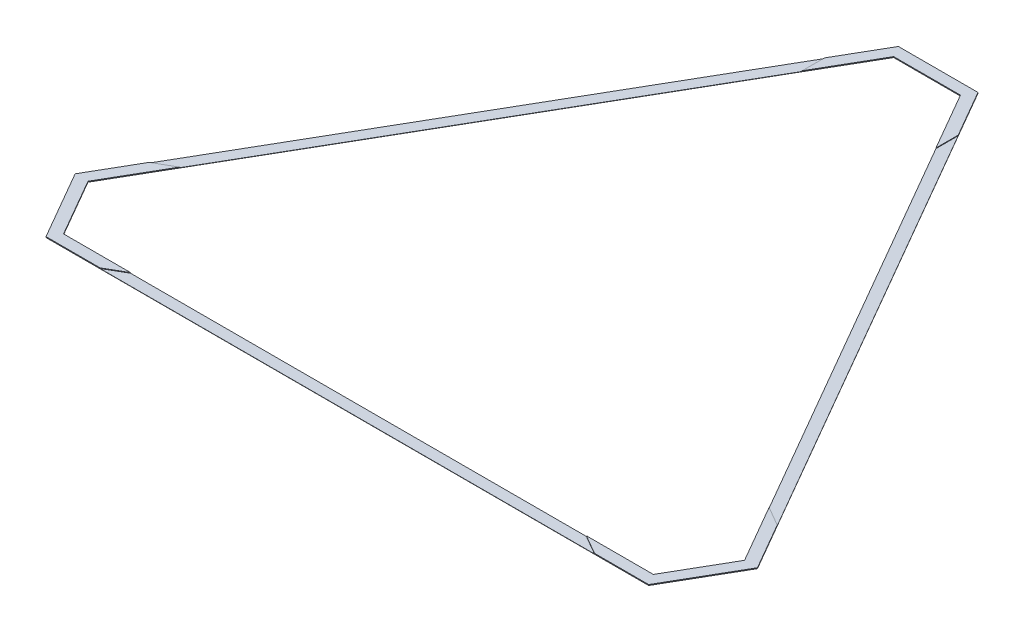
SolidWorks part; units mm, degrees
ref_plane "Front Plane" through (0, 0, 0) normal (0, 0, 1) x (1, 0, 0)
ref_plane "Top Plane" through (0, 0, 0) normal (0, 1, 0) x (1, 0, 0)
ref_plane "Right Plane" through (0, 0, 0) normal (1, 0, 0) x (0, 0, -1)
sketch "Sketch1" plane through (0, 0, 0) normal (0, 1, 0) x (1, 0, 0)
  line L0 (-152.4, 1642.446) -> (-1498.6, -689.2408)
  line L1 (-1498.6, -689.2408) -> (-1346.2, -953.2053)
  line L2 (-1346.2, -953.2053) -> (1346.2, -953.2053)
  line L3 (1346.2, -953.2053) -> (1498.6, -689.2408)
  line L4 (1498.6, -689.2408) -> (152.4, 1642.446)
  line L5 (152.4, 1642.446) -> (-152.4, 1642.446)
  line L6 (0, 0) -> (0, -953.2053) construction
  line L7 (0, 0) -> (825.5, 476.6026) construction
  line L8 (0, 0) -> (-825.5, 476.6026) construction
  line L9 (-181.7294, 1693.246) -> (-1557.2588, -689.2408)
  line L10 (-1557.2588, -689.2408) -> (-1375.5294, -1004.0053)
  line L11 (-1375.5294, -1004.0053) -> (1375.5294, -1004.0053)
  line L12 (1375.5294, -1004.0053) -> (1557.2588, -689.2408)
  line L13 (1557.2588, -689.2408) -> (181.7294, 1693.246)
  line L14 (181.7294, 1693.246) -> (-181.7294, 1693.246)
  dimension "D1" = 304.8
  dimension "D2" = 2692.4
  dimension "D3" = 50.8
extrude "Boss-Extrude1" add sketch "Sketch1" along normal blind 1.27 contours L13 L14 L9 L10 L11 L12 L5 L4 L3 L2 L1 L0 region at (0, 0, -1652.0449)
sketch "Sketch2" plane through (0, 1.27, 0) normal (0, 1, 0) x (1, 0, 0)
  line L0 (-305.308, 1479.2016) -> (-305.308, 1377.6016)
  line L1 (-181.7294, 1693.246) -> (-1557.2588, -689.2408) construction
  line L2 (-152.4, 1642.446) -> (-1498.6, -689.2408) construction
  line L3 (305.308, 1479.2016) -> (305.308, 1377.6016)
  line L4 (1557.2588, -689.2408) -> (181.7294, 1693.246) construction
  line L5 (1498.6, -689.2408) -> (152.4, 1642.446) construction
  line L6 (1375.5294, -1004.0053) -> (1557.2588, -689.2408) construction
  line L7 (1346.2, -953.2053) -> (1498.6, -689.2408) construction
  line L10 (-1375.5294, -1004.0053) -> (1375.5294, -1004.0053) construction
  line L11 (-1346.2, -953.2053) -> (1346.2, -953.2053) construction
  line L12 (-1498.6, -689.2408) -> (-1346.2, -953.2053) construction
  line L13 (-1557.2588, -689.2408) -> (-1375.5294, -1004.0053) construction
  line L14 (181.7294, 1693.246) -> (-181.7294, 1693.246) construction
  line L15 (152.4, 1642.446) -> (-152.4, 1642.446) construction
  line L16 (1375.5294, -1004.0053) -> (1557.2588, -689.2408)
  line L17 (1346.2, -953.2053) -> (1498.6, -689.2408)
  line L18 (-1375.5294, -1004.0053) -> (1375.5294, -1004.0053)
  line L19 (-1346.2, -953.2053) -> (1346.2, -953.2053)
  line L20 (-1498.6, -689.2408) -> (-1346.2, -953.2053)
  line L21 (-1557.2588, -689.2408) -> (-1375.5294, -1004.0053)
  line L22 (-181.7294, 1693.246) -> (-1557.2588, -689.2408)
  line L23 (181.7294, 1693.246) -> (-181.7294, 1693.246)
  line L24 (1557.2588, -689.2408) -> (181.7294, 1693.246)
  line L25 (1498.6, -689.2408) -> (152.4, 1642.446)
  line L26 (152.4, 1642.446) -> (-152.4, 1642.446)
  line L27 (-152.4, 1642.446) -> (-1498.6, -689.2408)
  line L28 (1433.6802, -475.1963) -> (1345.692, -424.3963)
  line L29 (1128.3722, -1004.0053) -> (1040.384, -953.2053)
  line L30 (-1128.3722, -1004.0053) -> (-1040.384, -953.2053)
  line L31 (-1433.6802, -475.1963) -> (-1345.692, -424.3963)
  point P24 (0, 0)
  line M15 (-152.4, 1642.446) -> (152.4, 1642.446)
  line M16 (152.4, 1642.446) -> (1498.6, -689.2408)
  line M17 (1498.6, -689.2408) -> (1346.2, -953.2053)
  line M18 (1346.2, -953.2053) -> (-1346.2, -953.2053)
  line M19 (-1346.2, -953.2053) -> (-1498.6, -689.2408)
  line M20 (-1498.6, -689.2408) -> (-152.4, 1642.446)
  line M21 (1557.2588, -689.2408) -> (181.7294, 1693.246)
  line M22 (181.7294, 1693.246) -> (-181.7294, 1693.246)
  line M23 (-181.7294, 1693.246) -> (-1557.2588, -689.2408)
  line M24 (-1557.2588, -689.2408) -> (-1375.5294, -1004.0053)
  line M25 (-1375.5294, -1004.0053) -> (1375.5294, -1004.0053)
  line M26 (1375.5294, -1004.0053) -> (1557.2588, -689.2408)
  dimension "D1" = 610.616
  dimension "D2" = 3
extrude "Boss-Extrude2" add sketch "Sketch2" along normal blind 2.6568 contours L3 L0 M21 M22 M23 M20 M15 M16 | L29 L18 L28 L25 M26 M21 M17 M18 | L31 L22 L30 M24 M25 M18 M19 M20 region at (-237.5659, 1.27, -1582.787) region at (-1385.8031, 1.27, 456.5219) region at (1488.7439, 1.27, 586.1015)
